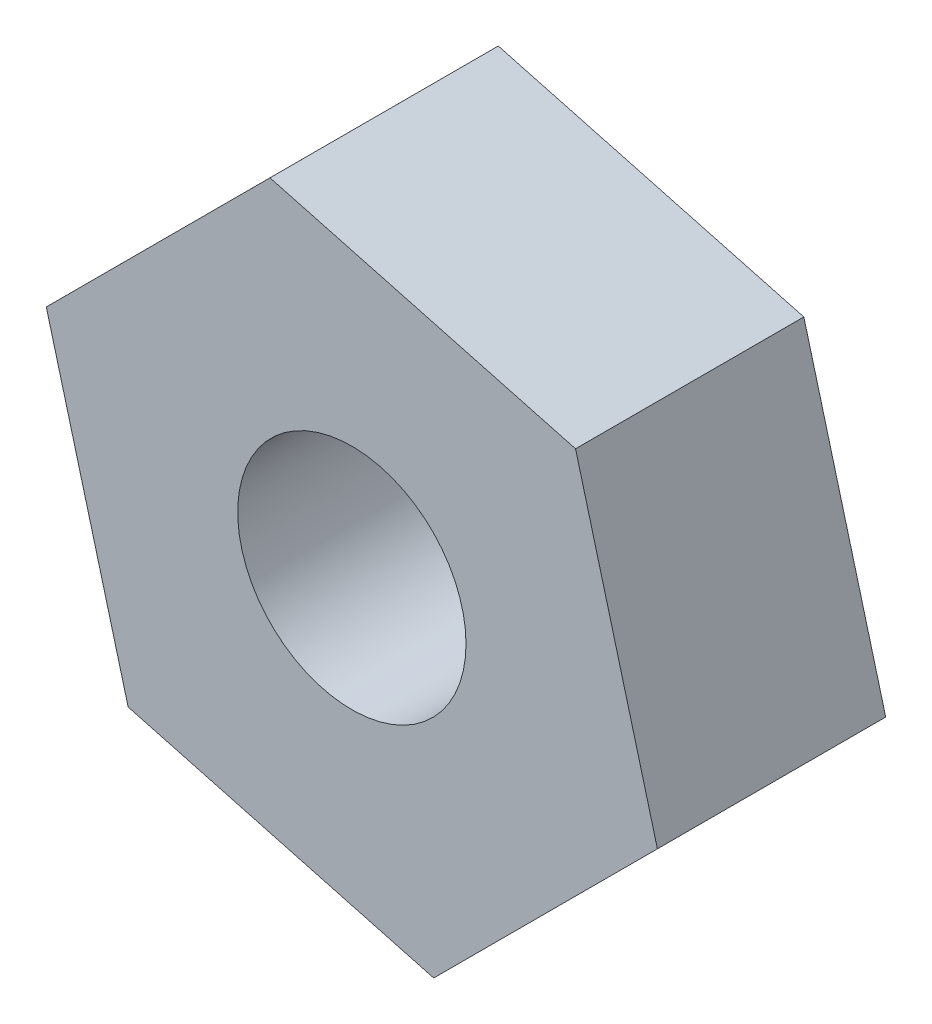
SolidWorks part; units mm, degrees
ref_plane "Alzado" through (0, 0, 0) normal (0, 0, 1) x (1, 0, 0)
ref_plane "Planta" through (0, 0, 0) normal (0, 1, 0) x (1, 0, 0)
ref_plane "Vista lateral" through (0, 0, 0) normal (1, 0, 0) x (0, 0, -1)
sketch "Croquis1" plane through (0, 0, 0) normal (0, 0, 1) x (1, 0, 0)
  circle A0 centre (0, 0) radius 2.5
  circle A1 centre (0, 0) radius 6
extrude "Saliente-Extruir1" add sketch "Croquis1" along normal blind 5
sketch "Croquis2" plane through (0, 0, 5) normal (0, 0, 1) x (1, 0, 0)
  line L8 (-6.6921, 1.7932) -> (-1.7931, 6.6921)
  line L9 (-1.7931, 6.6921) -> (4.899, 4.8989)
  line L10 (4.899, 4.8989) -> (6.6921, -1.7932)
  line L11 (6.6921, -1.7932) -> (1.7931, -6.6921)
  line L12 (1.7931, -6.6921) -> (-4.899, -4.8989)
  line L13 (-4.899, -4.8989) -> (-6.6921, 1.7932)
  circle A3 centre (0, 0) radius 2.5
  point P13 (0, 0)
  point P15 (-4.2426, 4.2426)
  point P28 (0, 0)
  dimension "D2" = 6
extrude "Saliente-Extruir2" add sketch "Croquis2" against normal blind 5
